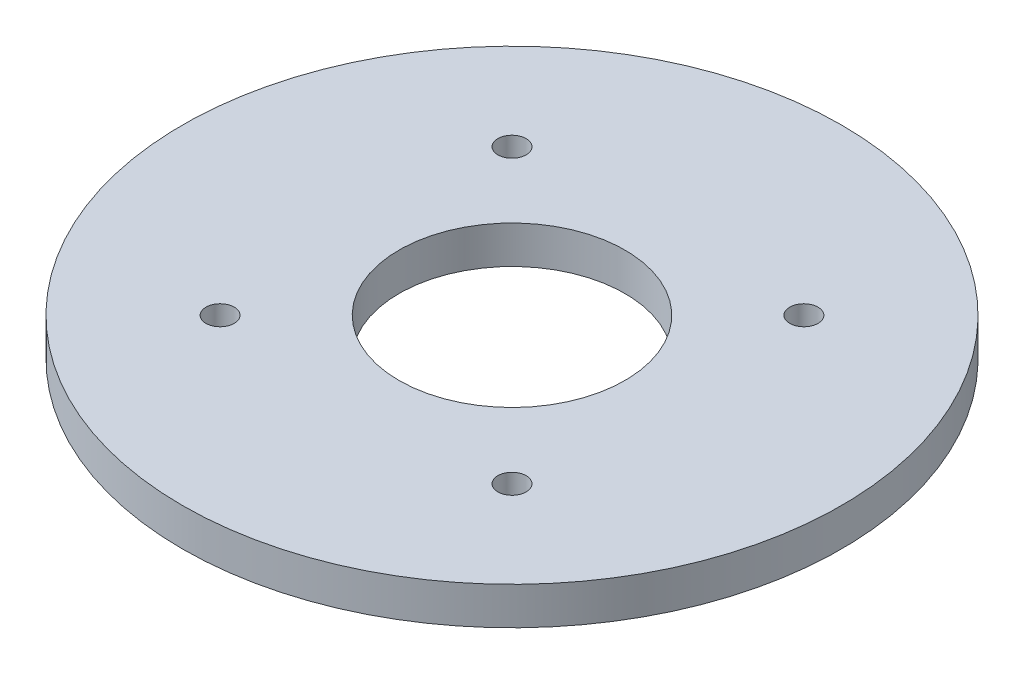
SolidWorks part; units mm, degrees
ref_plane "Front Plane" through (0, 0, 0) normal (0, 0, 1) x (1, 0, 0)
ref_plane "Top Plane" through (0, 0, 0) normal (0, 1, 0) x (1, 0, 0)
ref_plane "Right Plane" through (0, 0, 0) normal (1, 0, 0) x (0, 0, -1)
sketch "Sketch2" plane through (0, -14.2468, 0) normal (0, 1, 0) x (1, 0, 0)
  circle A0 centre (-1.2, 0) radius 35
  circle A1 centre (-1.2, 0) radius 12
  circle A2 centre (14.3, 15.5) radius 1.5
  circle A3 centre (-16.7, 15.5) radius 1.5
  circle A4 centre (-16.7, -15.5) radius 1.5
  circle A5 centre (14.3, -15.5) radius 1.5
extrude "Boss-Extrude1" add sketch "Sketch2" along normal blind 4
